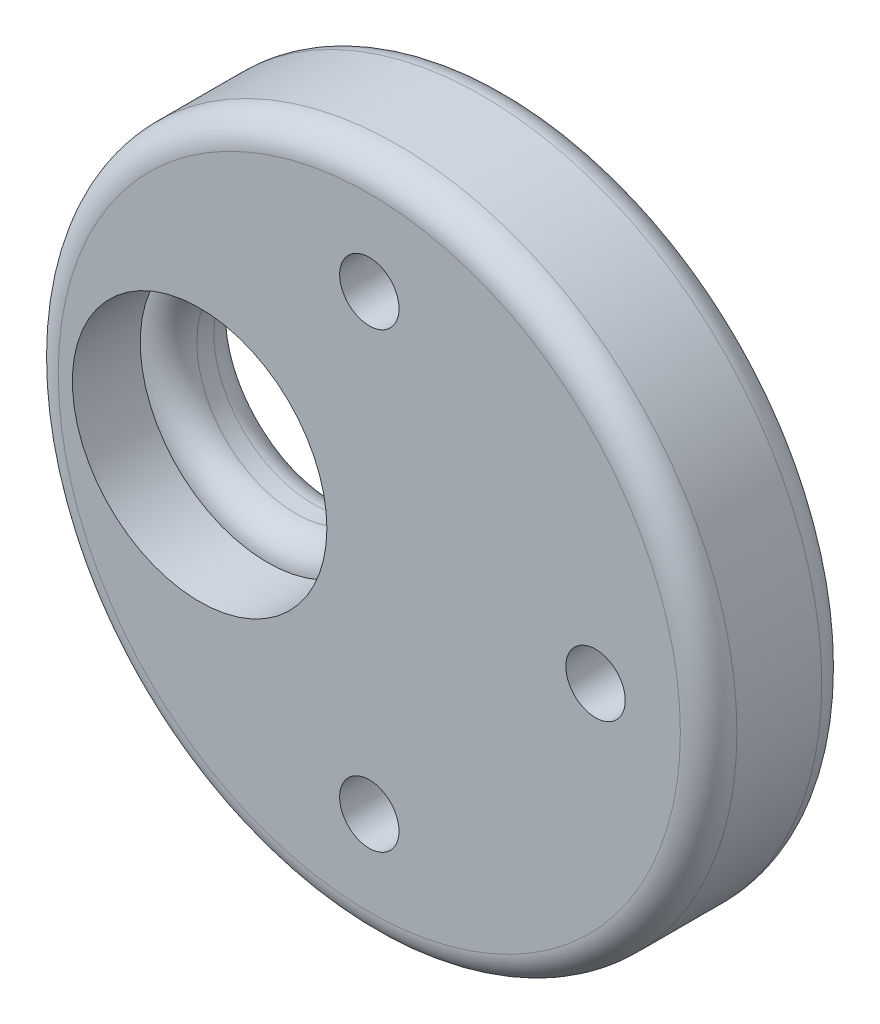
SolidWorks part; units mm, degrees
ref_plane "Front Plane" through (0, 0, 0) normal (0, 0, 1) x (1, 0, 0)
ref_plane "Top Plane" through (0, 0, 0) normal (0, 1, 0) x (1, 0, 0)
ref_plane "Right Plane" through (0, 0, 0) normal (1, 0, 0) x (0, 0, -1)
sketch "Sketch1" plane through (0, 0, 0) normal (0, 0, 1) x (1, 0, 0)
  circle A0 centre (0, 0) radius 12
  circle A1 centre (0, 8) radius 1.05
  circle A2 centre (8, 0) radius 1.05
  circle A3 centre (0, -8) radius 1.05
  circle A4 centre (-8, 0) radius 1.05 [skipped]
  dimension "D1" = 24
  dimension "D4" = 2.1
  dimension "D3" = 8
  dimension "D2" = 3
extrude "Boss-Extrude1" add sketch "Sketch1" along normal blind 5
hole_wizard "Hole2" positions "Sketch7" profile "Sketch6" legacy
sketch "Sketch7" plane through (0, 0, 5) normal (0, 0, 1) x (1, 0, 0)
  line L0 (0, 0) -> (-14.5014, 0) construction
  point P0 (-6, 0)
  dimension "D1" = 6
sketch "Sketch6" plane through (-6, 0, 5) normal (1, 0, 0) x (0, -1, 0)
  line L0 (0, 0) -> (0, 8)
  line L1 (0, 8) -> (3.5, 8)
  line L2 (3.5, 8) -> (3.5, 2.4)
  line L3 (3.5, 2.4) -> (4.5, 2.4)
  line L4 (4.5, 2.4) -> (4.5, 0)
  line L5 (4.5, 0) -> (0, 0)
  line L6 (0, 110) -> (0, -10) construction
  dimension "Diameter" = 7
  dimension "Depth" = 8
  dimension "C-Bore Diameter" = 9
  dimension "C-Bore Depth" = 2.4
sketch "Sketch8" plane through (0, 0, 0) normal (0, 0, -1) x (-1, 0, 0)
  circle A0 centre (0, 8) radius 2.15
  circle A1 centre (0, -8) radius 2.15
  circle A2 centre (-8, 0) radius 2.15
  dimension "D1" = 4.3
extrude "Cut-Extrude1" cut sketch "Sketch8" against normal blind 3
fillet "Fillet1" radius 1 2 edges at (-2.5, 0, 0) (-2.5, 0, 2.6)
fillet "Fillet2" radius 1 2 edges at (12, 0, 0) (12, 0, 5)
